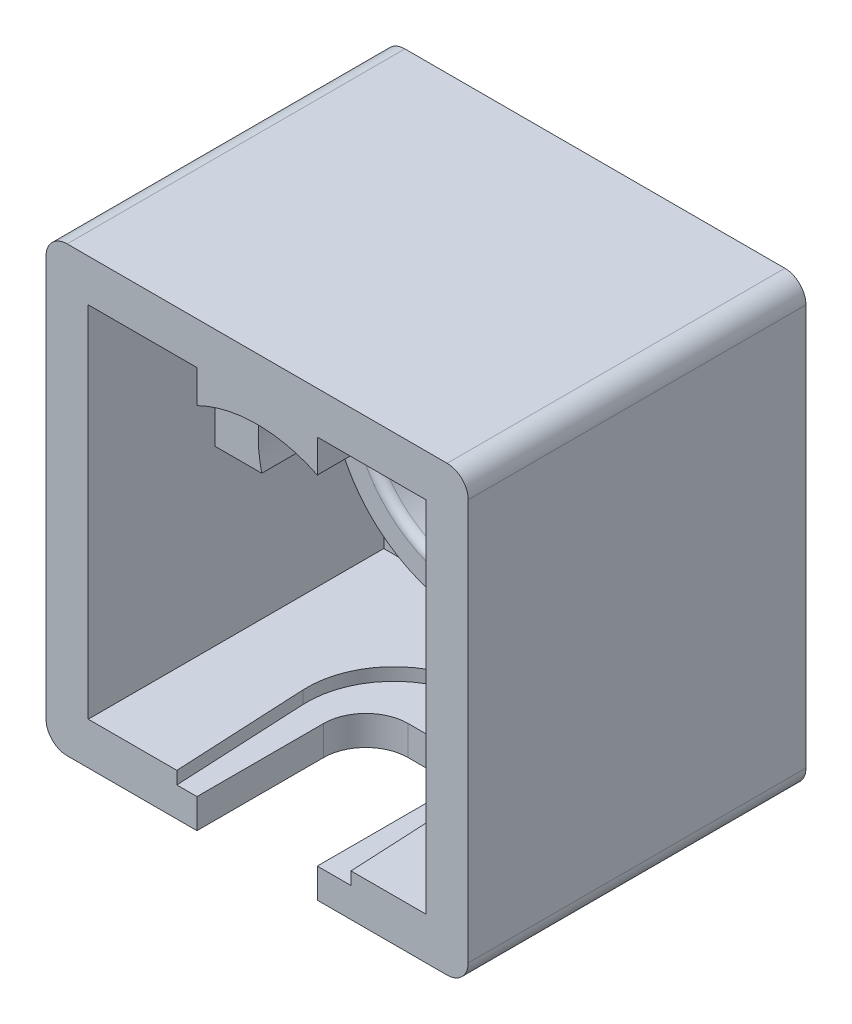
SolidWorks part; units mm, degrees
ref_plane "Front Plane" through (0, 0, 0) normal (0, 0, 1) x (1, 0, 0)
ref_plane "Top Plane" through (0, 0, 0) normal (0, 1, 0) x (1, 0, 0)
ref_plane "Right Plane" through (0, 0, 0) normal (1, 0, 0) x (0, 0, -1)
sketch "Sketch1" plane through (0, 0, 0) normal (0, 0, 1) x (1, 0, 0)
  line L0 (54.25, -85) -> (54.25, -95)
  line L1 (-10, 10) -> (90, 10)
  line L2 (-10, 10) -> (-10, -95)
  line L4 (90, 10) -> (90, -95)
  line L5 (0, 0) -> (80, 0)
  line L6 (0, 0) -> (0, -85)
  line L7 (0, -85) -> (80, -85)
  line L8 (80, 0) -> (80, -85)
  line L9 (-10, -95) -> (90, -95)
  line L10 (25.75, -85) -> (25.75, -95)
  line L11 (25.75, 0) -> (25.75, -15.8532)
  line L12 (54.25, 0) -> (54.25, -7.7906)
  line L13 (54.25, -7.7906) -> (54.25, -15.8532)
  line L14 (0, -37) -> (80, -37) construction
  line L15 (80, -30) -> (64.5204, -30)
  line L16 (80, -44) -> (64.5204, -44)
  line L17 (0, -30) -> (15.4796, -30)
  line L18 (0, -44) -> (15.4796, -44)
  line L19 (68.9, -30) -> (68.9, -44)
  line L20 (11.1, -30) -> (11.1, -44)
  circle A0 centre (40, -37) radius 32.5
  circle A3 centre (6, -6) radius 2
  circle A4 centre (6, -6) radius 4
  circle A5 centre (74, -79) radius 2
  circle A6 centre (74, -79) radius 4
  circle A7 centre (40, -37) radius 25.5
  circle A8 centre (40, -20.8872) radius 4
  circle A9 centre (40, -37) radius 29.7357
  point P12 (40, -85)
  dimension "D7" = 37
  dimension "D8" = 40
  dimension "D9" = 65
  dimension "D10" = 14.25
  dimension "D12" = 6
  dimension "D14" = 6
  dimension "D16" = 51
  dimension "D17" = 7
  dimension "D1" = 100
  dimension "D2" = 58
  dimension "D3" = 80
  dimension "D4" = 10
  dimension "D5" = 85
  dimension "D6" = 10
  dimension "D11" = 14.25
  dimension "D13" = 6
  dimension "D15" = 6
  dimension "D18" = 7
  dimension "D19" = 11.1
  dimension "D20" = 11.1
extrude "Boss-Extrude1" add sketch "Sketch1" against normal blind 10 contours L1 L4 L9 L2
extrude "Boss-Extrude2" add sketch "Sketch1<3>" along normal blind 70 contours L9 L4 L1 L2 | L5 L8 L7 L6
sketch "Sketch1<3>" plane through (0, 0, 0) normal (0, 0, 1) x (1, 0, 0) same geometry as "Sketch1"
extrude "Cut-Extrude1" cut sketch "Sketch1<6>" along normal blind 80 contours L7 L10 L9 L0 region at (40, -90, 0)
sketch "Sketch1<6>" plane through (0, 0, 0) normal (0, 0, 1) x (1, 0, 0) same geometry as "Sketch1"
extrude "Boss-Extrude4" add sketch "Sketch1<7>" along normal blind 30 contours L7 L10 L9 L0 region at (40, -90, 0)
sketch "Sketch1<7>" plane through (0, 0, 0) normal (0, 0, 1) x (1, 0, 0) same geometry as "Sketch1"
extrude "Cut-Extrude2" cut sketch "Sketch1<8>" against normal blind 30 contours A3 | A5
sketch "Sketch1<8>" plane through (0, 0, 0) normal (0, 0, 1) x (1, 0, 0) same geometry as "Sketch1"
extrude "Cut-Extrude3" cut sketch "Sketch1<9>" against normal blind 4 contours A6 | A4
sketch "Sketch1<9>" plane through (0, 0, 0) normal (0, 0, 1) x (1, 0, 0) same geometry as "Sketch1"
extrude "Boss-Extrude6" add sketch "Sketch1<11>" along normal blind 20 contours A0 | A7
sketch "Sketch1<11>" plane through (0, 0, 0) normal (0, 0, 1) x (1, 0, 0) same geometry as "Sketch1"
fillet "Fillet1" radius 10 2 edges at (25.75, -90, 30) (54.25, -90, 30)
extrude "Boss-Extrude7" add sketch "Sketch1<12>" along normal blind 19 contours A8
sketch "Sketch1<12>" plane through (0, 0, 0) normal (0, 0, 1) x (1, 0, 0) same geometry as "Sketch1"
extrude "Boss-Extrude13" add sketch "Sketch1<18>" along normal blind 70 contours A0 L12 L5 L11 region at (40, -2.8718, 0)
sketch "Sketch1<18>" plane through (0, 0, 0) normal (0, 0, 1) x (1, 0, 0) same geometry as "Sketch1"
extrude "Boss-Extrude17" add sketch "Sketch1<24>" along normal blind 40 contours A0 L14 L20 L17 | L14 A0 L18 L20 | L14 L6 L18 A0 | L6 L14 A0 L17 | L19 L14 A0 L15 | A0 L14 L8 L15 | L14 A0 L16 L8 | L14 L19 L16 A0 region at (76.1201, -40.5573, 0) region at (3.8799, -40.5573, 0) region at (76.1201, -33.4427, 0) region at (70.851, -40.5151, 0) region at (3.8799, -33.4427, 0) region at (9.149, -40.5151, 0) region at (70.851, -33.4849, 0) region at (9.149, -33.4849, 0)
sketch "Sketch1<24>" plane through (0, 0, 0) normal (0, 0, 1) x (1, 0, 0) same geometry as "Sketch1"
extrude "Cut-Extrude4" cut sketch "Sketch1<25>" along normal blind 40 contours A9 L14 L20 | L14 A9 L20 | L19 L14 A9 | L14 L19 A9 region at (69.2347, -39.63, 0) region at (10.7653, -39.63, 0) region at (69.2347, -34.37, 0) region at (10.7653, -34.37, 0)
sketch "Sketch1<25>" plane through (0, 0, 0) normal (0, 0, 1) x (1, 0, 0) same geometry as "Sketch1"
ref_plane "Plane1" through (0, -85, 0) normal (0, 1, 0) x (1, 0, 0)
sketch "Sketch2" plane through (0, -85, 0) normal (0, 1, 0) x (1, 0, 0)
  line L0 (40, -37.5846) -> (42.2465, -82.7753) construction
  line L1 (60.5753, -36.5618) -> (62.8218, -81.7524)
  line L2 (19.4247, -38.6075) -> (21.6712, -83.7981)
  arc A0 (60.5753, -36.5618) -> (19.4247, -38.6075) centre (40, -37.5846) ccw
  arc A1 (21.6712, -83.7981) -> (62.8218, -81.7524) centre (42.2465, -82.7753) ccw
  point P4 (41.1233, -60.1799)
extrude "Cut-Extrude5" cut sketch "Sketch2" against normal blind 3
fillet "Fillet2" radius 5 4 edges at (90, -95, 30) (90, 10, 30) (-10, 10, 30) (-10, -95, 30)
fillet "Fillet3" radius 2 1 edges at (65.5, -37, 20)
